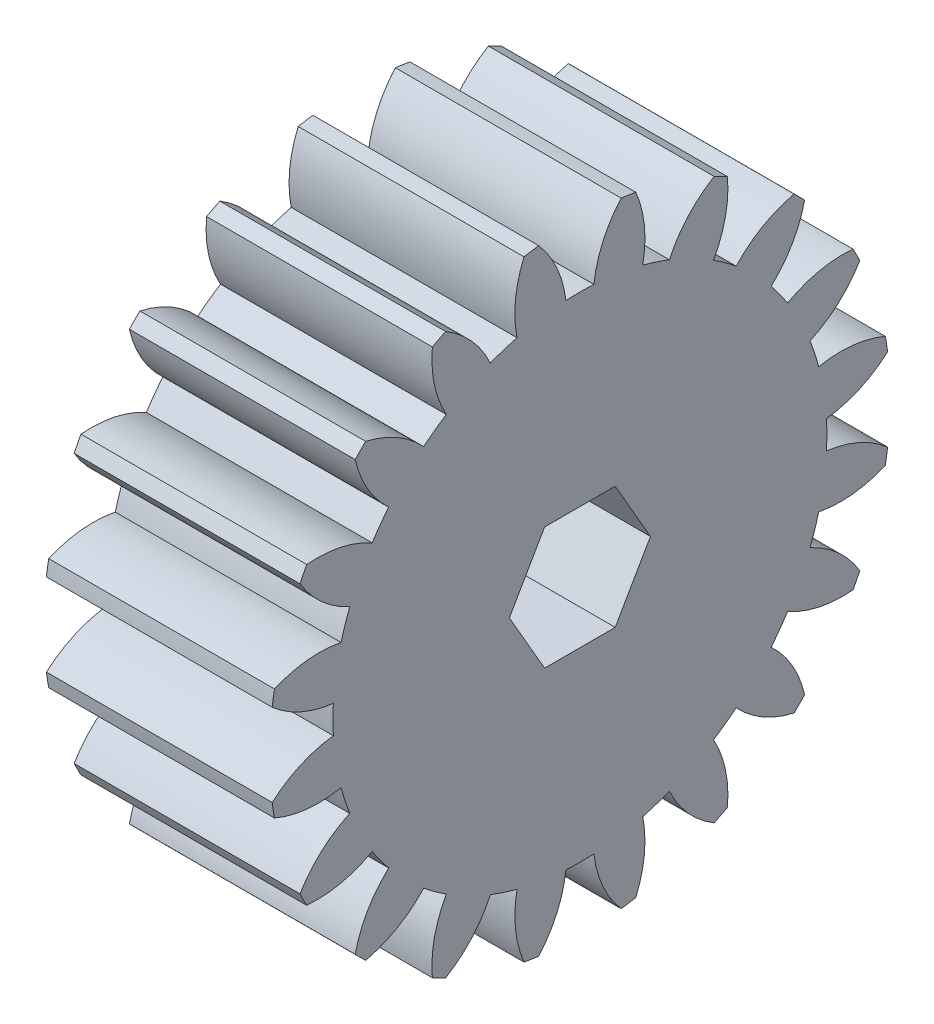
SolidWorks part; units mm, degrees
ref_plane "Plane1" through (0, 0, 0) normal (0, 0, 1) x (1, 0, 0)
ref_plane "Plane2" through (0, 0, 0) normal (0, 1, 0) x (1, 0, 0)
ref_plane "Plane3" through (0, 0, 0) normal (1, 0, 0) x (0, 0, -1)
sketch "HoldingSke" plane through (0, 0, 0) normal (0, 1, 0) x (1, 0, 0)
  line L0 (0, 0) -> (0.6265, -0.228)
  line L1 (-15, 0) -> (100, 0) construction
  line L2 (0, 0) -> (-2.1039, 2.3779)
  line L3 (0, 0) -> (-11.863, 4.5341)
  line L4 (0, 0) -> (8.1152, 2.9537)
  line L5 (0, 0) -> (-46.8476, -17.4728)
  line L6 (0, 0) -> (-9.9476, -6.7116)
  line L7 (-2.1039, 2.3779) -> (8.6586, 51.2059)
  line L8 (-76.2, 54.61) -> (-75.3, 54.61)
  line L9 (-71.009, 38.7566) -> (-53.1078, 45.2721)
  line L10 (-76.2, 71.12) -> (104.1128, 71.12)
  line L11 (0, 0) -> (-12, 0)
  line L12 (-76.2, 101.6) -> (-76.147, 101.6)
  line L13 (24.9733, 27.94) -> (52.9518, 28.4284)
  line L14 (24.9733, 27.94) -> (24.9743, 27.94)
  line L15 (24.9733, 27.94) -> (100.4006, 29.5858)
  line L16 (-63.627, -1.5) -> (-12.827, -1.5)
  circle A0 centre (0, 0) radius 2.5
  circle A1 centre (0, 0) radius 13.124
  circle A2 centre (0, 0) radius 37.5
  circle A3 centre (0, 0) radius 2.5
  dimension "MHD" = 26.248
  dimension "Hub_dia" = 75
  dimension "Bore" = 5
  dimension "MBD" = 5
  dimension "Num_teeth" = 20
  dimension "Pitch" = 0.6667
  dimension "Overall_len" = 50
  dimension "Show_teeth" = 20
  dimension "Thickness" = 12
  dimension "OAL" = 50.0001
  dimension "T_dim" = 0.9
  dimension "Ap" = 20
  dimension "H" = 19.05
  dimension "Pitch_radius" = 180.3128
  dimension "Width" = 12
  dimension "Backlash" = 0.053
  dimension "Addendum_fac" = 1
  dimension "Dedendum_fac" = 1.25
  dimension "Clearance_fac" = 0.25
  dimension "Dedendum_add" = 0.001
  dimension "Module" = 1.5
sketch "BasProSke" plane through (0, 0, 0) normal (0, 1, 0) x (1, 0, 0)
  line L0 (-10, 0) -> (60, 0) construction
  line L1 (0, 0) -> (0, 16.5)
  line L2 (0, 0) -> (12, 0)
  line L3 (12, 0) -> (12, 16.5)
  line L4 (12, 16.5) -> (0, 16.5)
  dimension "Thickness" = 12
  dimension "Diameter" = 33
revolve "Base-Revolve" add sketch "BasProSke" angle 360 about L0
sketch "TooCutSke" plane through (0, 0, 0) normal (1, 0, 0) x (0, 0, -1)
  line L1 (0, 0) -> (0, 107) construction
  line L2 (0, 0) -> (-1.2696, 14.9462) construction
  line L3 (0, 0) -> (-4.6808, 29.5532) construction
  line L4 (-1.2696, 14.9462) -> (-2.3404, 14.7766) construction
  arc A0 (0.7438, 13.1029) -> (-0.7438, 13.1029) centre (0, 0) ccw
  arc A1 (2.21, 16.377) -> (-2.21, 16.377) centre (0, 0) ccw
  circle A2 centre (0, 0) radius 15 construction
  circle A3 centre (0, 0) radius 14.0954 construction
  arc A4 (-0.7438, 13.1029) -> (-2.21, 16.377) centre (-6.7025, 12.3999) ccw
  arc A5 (2.21, 16.377) -> (0.7438, 13.1029) centre (6.7025, 12.3999) ccw
  dimension "Root_dia" = 26.248
  dimension "Overcut_dia" = 33.0508
  dimension "Pitch_dia" = 30
  dimension "Base_dia" = 28.1908
  dimension "Flank_rad" = 6
  dimension "Half_ang" = 9
  dimension "Half_CT" = 1.0841
extrude "ToothCut" cut sketch "TooCutSke" along normal through all
fillet "Breaks" [suppressed] radius 0.03 tangent propagation no
fillet "RootFillets" [suppressed] radius 0.376
pattern_circular "TeethCuts" count 20 every 18 about axis through (-10, 0, 0) along (1, 0, 0) of "ToothCut", "RootFillets", "Breaks"
sketch "HubNeaOneSke" plane through (0, 0, 0) normal (-1, 0, 0) x (0, 0, 1)
  circle A0 centre (0, 0) radius 13.124
  dimension "Diameter" = 26.248
extrude "HubNearOne" [suppressed] add sketch "HubNeaOneSke" along normal blind 38.0001
sketch "HubNeaBotSke" plane through (0, 0, 0) normal (-1, 0, 0) x (0, 0, 1)
  circle A0 centre (0, 0) radius 13.124
  dimension "Diameter" = 26.248
extrude "HubNearBoth" [suppressed] add sketch "HubNeaBotSke" along normal blind 19
ref_plane "FarPln" through (12, 0, 0) normal (1, 0, 0) x (0, 0, -1)
sketch "HubFarSke" plane through (12, 0, 0) normal (1, 0, 0) x (0, 0, -1)
  circle A0 centre (0, 0) radius 13.124
  dimension "Diameter" = 26.248
extrude "HubFar" [suppressed] add sketch "HubFarSke" along normal blind 19
sketch "BorSke" plane through (0, 0, 0) normal (1, 0, 0) x (0, 0, -1)
  circle A0 centre (0, 0) radius 2.5
  dimension "Diameter" = 5
extrude "Bore" cut sketch "BorSke" along normal mid plane 100.0001
sketch "KeySke" plane through (0, 0, 0) normal (1, 0, 0) x (0, 0, -1)
  line L0 (-1, 0) -> (-1, 3.4)
  line L1 (-1, 3.4) -> (1, 3.4)
  line L2 (1, 3.4) -> (1, 0)
  line L3 (0, 0) -> (0, 34) construction
  line L4 (-1, 0) -> (1, 0)
  dimension "Offset" = 3.4
  dimension "Width" = 2
extrude "Keyway" [suppressed] cut sketch "KeySke" along normal mid plane 100.0001
pattern_circular "Keyway2" [suppressed] count 2 every 90 about axis through (-10, 0, 0) along (1, 0, 0) reverse direction yes
sketch "Sketch1" plane through (12, 0, 0) normal (1, 0, 0) x (0, 0, -1)
  line L1 (3.75, 0) -> (1.875, 3.2476)
  line L2 (1.875, 3.2476) -> (-1.875, 3.2476)
  line L3 (-1.875, 3.2476) -> (-3.75, 0)
  line L4 (-3.75, 0) -> (-1.875, -3.2476)
  line L5 (-1.875, -3.2476) -> (1.875, -3.2476)
  line L6 (1.875, -3.2476) -> (3.75, 0)
  circle A0 centre (0, 0) radius 3.2476 construction
  circle A1 centre (0, 0) radius 3.75 construction
  dimension "D1" = 7.5
extrude "Cut-Extrude1" cut sketch "Sketch1" against normal through all
equation "' \"Module@HoldingSke\" = 6.35"
equation "' \"Num_teeth@HoldingSke\" = 12"
equation "' \"Ap@HoldingSke\" =  20"
equation "' \"Ap@HoldingSke\" = 20"
equation "' \"Width@HoldingSke\" = 0.5 * 25.4"
equation "' \"Hub_dia@HoldingSke\"= 1 * 25.4"
equation "' \"Hub_dia@HoldingSke\" = 1 * 25.4"
equation "' \"Overall_len@HoldingSke\" = 1.0 * 25.4"
equation "' \"Bore@HoldingSke\" = 0.75 * 25.4"
equation "' \"T_dim@HoldingSke\" = 0.1 * 25.4"
equation "' \"Width@KeySke\" = 0.25 * 25.4"
equation "' \"Show_teeth@HoldingSke\" = 13"
equation "' \"Backlash@HoldingSke\" = 0.009 * 25.4"
equation "' \"Addendum_fac@HoldingSke\" = 1.0"
equation "' \"Dedendum_fac@HoldingSke\" = 1.25"
equation "' \"Dedendum_add@HoldingSke\" = 0.00005 * 25.4"
equation "' \"Clearance_fac@HoldingSke\" = 0.25"
equation "\"Pitch@HoldingSke\" = 1 / \"Module@HoldingSke\""
equation "\"Overcut_dia@TooCutSke\" = (\"Num_teeth@HoldingSke\" + 2 * \"Addendum_fac@HoldingSke\") / \"Pitch@HoldingSke\" + 0.002 * 25.4"
equation "\"Pitch_dia@TooCutSke\" = \"Num_teeth@HoldingSke\" / \"Pitch@HoldingSke\""
equation "\"Base_dia@TooCutSke\" = \"Num_teeth@HoldingSke\" / \"Pitch@HoldingSke\" * cos((\"Ap@HoldingSke\"  * 3.14159265 / 180))"
equation "\"Root_dia@TooCutSke\" = (\"Num_teeth@HoldingSke\" + 2) / \"Pitch@HoldingSke\" - 2 * (\"Addendum_fac@HoldingSke\" + \"Dedendum_fac@HoldingSke\") / \"Pitch@HoldingSke\" - \"Dedendum_add@HoldingSke\" * 2"
equation "\"Half_ang@TooCutSke\" = 180 / \"Num_teeth@HoldingSke\""
equation "\"Half_CT@TooCutSke\" = \"Num_teeth@HoldingSke\" / \"Pitch@HoldingSke\" * sin((3.14159265 / 2 / \"Num_teeth@HoldingSke\")) / 2 - 7 * \"Backlash@HoldingSke\" / 4"
equation "\"Flank_rad@TooCutSke\" = \"Num_teeth@HoldingSke\" / \"Pitch@HoldingSke\" / 5"
equation "\"Radius@RootFillets\" = \"Clearance_fac@HoldingSke\" / \"Pitch@HoldingSke\" + \"Dedendum_add@HoldingSke\""
equation "\"Break_rad@Breaks\" = 0.02 / \"Pitch@HoldingSke\""
equation "\"Thickness@HoldingSke\" = \"Width@HoldingSke\""
equation "\"OAL@HoldingSke\" = \"Thickness@HoldingSke\""
equation "\"MHD@HoldingSke\" = (\"Num_teeth@HoldingSke\" + 2) / \"Pitch@HoldingSke\" - 2 * (\"Addendum_fac@HoldingSke\" + \"Dedendum_fac@HoldingSke\")  / \"Pitch@HoldingSke\" - \"Dedendum_add@HoldingSke\" * 2"
equation "\"MBD@HoldingSke\" = (\"Num_teeth@HoldingSke\" + 2) / \"Pitch@HoldingSke\" - 2 * (\"Addendum_fac@HoldingSke\" + \"Dedendum_fac@HoldingSke\")  / \"Pitch@HoldingSke\" - \"Dedendum_add@HoldingSke\" * 2 - 0.002 * 25.4"
equation "\"MHD@HoldingSke\" = ((sgn( \"MHD@HoldingSke\" - \"Hub_dia@HoldingSke\" )-1)*( \"MHD@HoldingSke\" - \"Hub_dia@HoldingSke\" ))/-2+ \"Hub_dia@HoldingSke\""
equation "\"MBD@HoldingSke\" = ((sgn( \"MBD@HoldingSke\" - \"Bore@HoldingSke\" )-1)*( \"MBD@HoldingSke\" - \"Bore@HoldingSke\" ))/-2+ \"Bore@HoldingSke\""
equation "\"OAL@HoldingSke\" = ((sgn( \"OAL@HoldingSke\" - \"Overall_len@HoldingSke\" )+1)*( \"OAL@HoldingSke\" - \"Overall_len@HoldingSke\" ))/2 + \"Overall_len@HoldingSke\" + 0.000002 * 25.4"
equation "\"Num_teeth@TeethCuts\" = int( \"Show_teeth@HoldingSke\" ) + 1"
equation "\"Num_teeth@TeethCuts\" = ((sgn( \"Num_teeth@TeethCuts\" - \"Num_teeth@HoldingSke\" )-1)*( \"Num_teeth@TeethCuts\" - \"Num_teeth@HoldingSke\" ))/-2+ \"Num_teeth@HoldingSke\""
equation "\"Num_teeth@TeethCuts\" = ((sgn( \"Num_teeth@TeethCuts\" - 2.0)+1)*( \"Num_teeth@TeethCuts\" - 2.0))/2 +2.0"
equation "\"Angle@TeethCuts\" = 360.0 / \"Num_teeth@HoldingSke\""
equation "\"Diameter@BasProSke\" = (\"Num_teeth@HoldingSke\" + 2 * \"Addendum_fac@HoldingSke\") / \"Pitch@HoldingSke\""
equation "\"Thickness@BasProSke\"  = \"Thickness@HoldingSke\""
equation "' \"Fillet_rad@BasProSke\" =  \"Thickness@HoldingSke\" * 0.05"
equation "' \"Fillet_rad@BasProSke\" = \"Thickness@HoldingSke\" * 0.05"
equation "\"MHD@HoldingSke\" = ((sgn( \"MHD@HoldingSke\" - \"Root_dia@TooCutSke\" )-1)*( \"MHD@HoldingSke\" - \"Root_dia@TooCutSke\" ))/-2+ \"Root_dia@TooCutSke\""
equation "\"Diameter@HubNeaOneSke\" = \"MHD@HoldingSke\""
equation "\"Length@HubNearOne\" = \"OAL@HoldingSke\" - \"Thickness@BasProSke\""
equation "\"Diameter@HubNeaBotSke\" = \"MHD@HoldingSke\""
equation "\"Length@HubNearBoth\" = ( \"OAL@HoldingSke\" - \"Thickness@BasProSke\" ) / 2.0"
equation "\"Thickness@FarPln\" = \"Thickness@BasProSke\""
equation "\"Diameter@HubFarSke\" = \"MHD@HoldingSke\""
equation "\"Length@HubFar\" = ( \"OAL@HoldingSke\" - \"Thickness@BasProSke\" ) / 2.0"
equation "\"Diameter@BorSke\" = \"MBD@HoldingSke\""
equation "\"D1@Bore\" = \"OAL@HoldingSke\" * 2.0"
equation "\"D1@Keyway\" = \"OAL@HoldingSke\" * 2.0"
equation "\"Offset@KeySke\" = \"T_dim@HoldingSke\" + \"MBD@HoldingSke\" / 2.0"
